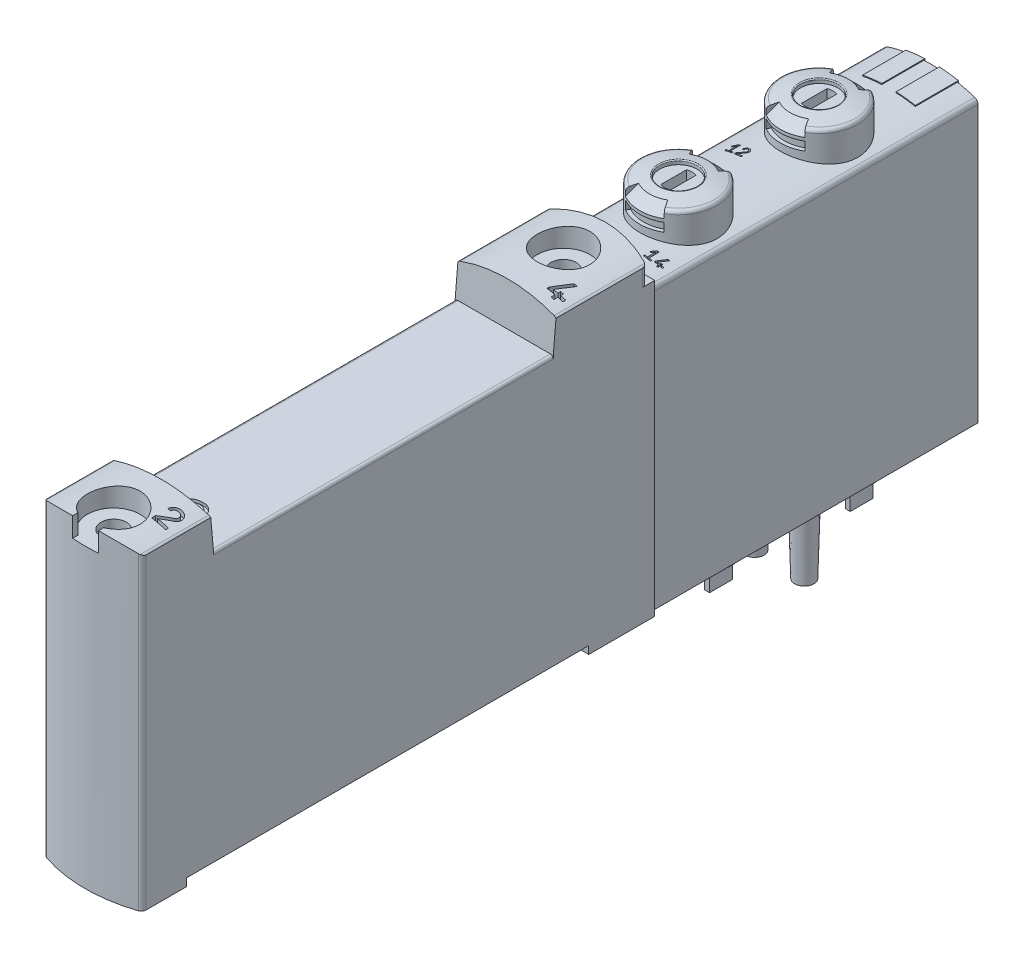
SolidWorks part; units mm, degrees
ref_plane "Ebene vorne" through (0, 0, 0) normal (0, 0, 1) x (1, 0, 0)
ref_plane "Ebene oben" through (0, 0, 0) normal (0, 1, 0) x (1, 0, 0)
ref_plane "Ebene rechts" through (0, 0, 0) normal (1, 0, 0) x (0, 0, -1)
ref_plane "Ebene1" through (0, 0, -23.2) normal (0, 0, 1) x (1, 0, 0)
sketch "Skizze1" plane through (0, 0, -23.2) normal (0, 0, 1) x (1, 0, 0)
  line L0 (-4.9, 29.2163) -> (-4.9, 0)
  line L1 (-4.9, 0) -> (4.9, 0)
  line L2 (4.9, 0) -> (4.9, 29.2163)
  arc A0 (4.9, 29.2163) -> (4.5517, 29.6927) centre (4.4, 29.2163) ccw
  arc A1 (4.5517, 29.6927) -> (-4.5517, 29.6927) centre (0, 15.4) ccw
  arc A2 (-4.5517, 29.6927) -> (-4.9, 29.2163) centre (-4.4, 29.2163) ccw
extrude "Aufsatz-Linear austragen1" add sketch "Skizze1" along normal blind 34
sketch "Skizze2" plane through (0, 0, 0) normal (1, 0, 0) x (0, 0, -1)
  line L0 (-10.88, 0.4) -> (-10.88, 0)
  line L1 (-10.88, 0) -> (23.22, 0)
  line L2 (23.22, 0) -> (23.22, 0.4)
  line L3 (23.22, 0.4) -> (-10.88, 0.4)
extrude "Schnitt-Linear austragen1" cut sketch "Skizze2" along normal blind 6 and the other way blind 6
sketch "Skizze3" plane through (0, 0, 0) normal (0, 1, 0) x (1, 0, 0)
  line L0 (-3.15, 2.4653) -> (-3.15, -2.4653)
  line L1 (3.15, -2.4653) -> (3.15, 2.4653)
  arc A0 (-3.15, -2.4653) -> (3.15, -2.4653) centre (0, 0) ccw
  arc A1 (3.15, 2.4653) -> (-3.15, 2.4653) centre (0, 0) ccw
extrude "Schnitt-Linear austragen2" cut sketch "Skizze3" along normal blind 1.9
sketch "Skizze4" plane through (0, 0, 0) normal (0, 1, 0) x (1, 0, 0)
  line L0 (-3.15, 17.1653) -> (-3.15, 12.2347)
  line L1 (3.15, 12.2347) -> (3.15, 17.1653)
  arc A0 (-3.15, 12.2347) -> (3.15, 12.2347) centre (0, 14.7) ccw
  arc A1 (3.15, 17.1653) -> (-3.15, 17.1653) centre (0, 14.7) ccw
extrude "Schnitt-Linear austragen3" cut sketch "Skizze4" along normal blind 1.9
sketch "Skizze5" plane through (0, 0, 0) normal (1, 0, 0) x (0, 0, -1)
  line L0 (0, 2.1) -> (3.05, 2.1)
  line L1 (3.05, 2.1) -> (3.05, 1.1)
  line L2 (3.05, 1.1) -> (2.25, 1.1)
  line L3 (2.25, 1.1) -> (2.25, -1.4)
  line L4 (2.25, -1.4) -> (2.65, -1.4)
  line L5 (2.65, -1.4) -> (2.65, -1.72)
  line L6 (2.65, -1.72) -> (2.4306, -2.1)
  line L7 (2.4306, -2.1) -> (0, -2.1)
  line L8 (0, -2.1) -> (0, 2.1)
  line L9 (0, -2.1) -> (0, 2.1) construction
revolve "Rotation1" add sketch "Skizze5" angle 360 about L9 reverse direction yes
sketch "Skizze6" plane through (0, 0, 0) normal (1, 0, 0) x (0, 0, -1)
  line L0 (14.7, 2.1) -> (17.75, 2.1)
  line L1 (17.75, 2.1) -> (17.75, 1.1)
  line L2 (17.75, 1.1) -> (16.95, 1.1)
  line L3 (16.95, 1.1) -> (16.95, -1.4)
  line L4 (16.95, -1.4) -> (17.35, -1.4)
  line L5 (17.35, -1.4) -> (17.35, -1.72)
  line L6 (17.35, -1.72) -> (17.1306, -2.1)
  line L7 (17.1306, -2.1) -> (14.7, -2.1)
  line L8 (14.7, -2.1) -> (14.7, 2.1)
  line L9 (14.7, -2.1) -> (14.7, 2.1) construction
revolve "Rotation2" add sketch "Skizze6" angle 360 about L9 reverse direction yes
ref_plane "Ebene2" through (0, 0, -7.35) normal (0, 0, 1) x (1, 0, 0)
sketch "Skizze7" plane through (0, 0, -7.35) normal (0, 0, 1) x (1, 0, 0)
  line L0 (2.6, 0.4) -> (3.8, 0.4)
  line L1 (3.8, 0.4) -> (3.6, -6.9)
  line L2 (2.6, -7.0623) -> (2.6, 0.4)
  line L3 (2.6, -7.0623) -> (2.6, 0.4) construction
  arc A0 (3.6, -6.9) -> (2.6, -7.0623) centre (2.6, -3.9) cw
revolve "Rotation3" add sketch "Skizze7" angle 360 about L3 reverse direction yes
sketch "Skizze8" plane through (0, 0, -7.35) normal (0, 0, 1) x (1, 0, 0)
  line L0 (-2.6, 0.4) -> (-1.4, 0.4)
  line L1 (-1.4, 0.4) -> (-1.6, -6.9)
  line L2 (-2.6, -7.0623) -> (-2.6, 0.4)
  line L3 (-2.6, -7.0623) -> (-2.6, 0.4) construction
  arc A0 (-1.6, -6.9) -> (-2.6, -7.0623) centre (-2.6, -3.9) cw
revolve "Rotation4" add sketch "Skizze8" angle 360 about L3 reverse direction yes
ref_plane "Ebene3" through (0, 0, 0) normal (0, 1, 0) x (1, 0, 0)
ref_plane "Ebene4" through (0, -2.1, 0) normal (0, -1, 0) x (-1, 0, 0)
sketch "Skizze9" plane through (0, -2.1, 0) normal (0, -1, 0) x (-1, 0, 0)
  line L0 (-1.25, -1.2) -> (-0.75, -1.2)
  line L1 (-0.75, -1.2) -> (-0.75, 1.2)
  line L2 (-0.75, 1.2) -> (-1.25, 1.2)
  line L3 (-1.25, 1.2) -> (-1.25, -1.2)
extrude "Aufsatz-Linear austragen2" add sketch "Skizze9" along normal blind 2.5
ref_plane "Ebene5" through (0, -2.1, 0) normal (0, -1, 0) x (-1, 0, 0)
sketch "Skizze10" plane through (0, -2.1, 0) normal (0, -1, 0) x (-1, 0, 0)
  line L0 (0.75, -1.2) -> (1.25, -1.2)
  line L1 (1.25, -1.2) -> (1.25, 1.2)
  line L2 (1.25, 1.2) -> (0.75, 1.2)
  line L3 (0.75, 1.2) -> (0.75, -1.2)
extrude "Aufsatz-Linear austragen3" add sketch "Skizze10" along normal blind 2.5
ref_plane "Ebene6" through (0, -2.1, 0) normal (0, -1, 0) x (-1, 0, 0)
sketch "Skizze11" plane through (0, -2.1, 0) normal (0, -1, 0) x (-1, 0, 0)
  line L0 (-1.25, 13.5) -> (-0.75, 13.5)
  line L1 (-0.75, 13.5) -> (-0.75, 15.9)
  line L2 (-0.75, 15.9) -> (-1.25, 15.9)
  line L3 (-1.25, 15.9) -> (-1.25, 13.5)
extrude "Aufsatz-Linear austragen4" add sketch "Skizze11" along normal blind 2.5
ref_plane "Ebene7" through (0, -2.1, 0) normal (0, -1, 0) x (-1, 0, 0)
sketch "Skizze12" plane through (0, -2.1, 0) normal (0, -1, 0) x (-1, 0, 0)
  line L0 (0.75, 13.5) -> (1.25, 13.5)
  line L1 (1.25, 13.5) -> (1.25, 15.9)
  line L2 (1.25, 15.9) -> (0.75, 15.9)
  line L3 (0.75, 15.9) -> (0.75, 13.5)
extrude "Aufsatz-Linear austragen5" add sketch "Skizze12" along normal blind 2.5
sketch "Skizze13" plane through (0, 0, 0) normal (1, 0, 0) x (0, 0, -1)
  line L0 (-3.2, 33.13) -> (-1.25, 33.13)
  line L1 (-1.25, 33.13) -> (-1.25, 33.4583)
  line L2 (0.85, 32.8364) -> (0.85, 28.4)
  line L3 (0.85, 28.4) -> (-3.2, 28.4)
  line L4 (-3.2, 28.4) -> (-3.2, 33.13)
  line L5 (-3.2, 28.4) -> (-3.2, 33.7) construction
  arc A0 (-1.25, 33.4583) -> (-1.1362, 33.5574) centre (-1.15, 33.4583) cw
  arc A1 (-1.1362, 33.5574) -> (0.55, 33.2237) centre (-3.2, 18.7) cw
  arc A2 (0.55, 33.2237) -> (0.85, 32.8364) centre (0.45, 32.8364) cw
revolve "Rotation5" add sketch "Skizze13" angle 360 about L5 reverse direction yes
sketch "Skizze14" plane through (0, 0, 0) normal (1, 0, 0) x (0, 0, -1)
  line L0 (11.5, 33.13) -> (13.45, 33.13)
  line L1 (13.45, 33.13) -> (13.45, 33.4583)
  line L2 (15.55, 32.8364) -> (15.55, 28.4)
  line L3 (15.55, 28.4) -> (11.5, 28.4)
  line L4 (11.5, 28.4) -> (11.5, 33.13)
  line L5 (11.5, 28.4) -> (11.5, 33.7) construction
  arc A0 (13.45, 33.4583) -> (13.5638, 33.5574) centre (13.55, 33.4583) cw
  arc A1 (13.5638, 33.5574) -> (15.25, 33.2237) centre (11.5, 18.7) cw
  arc A2 (15.25, 33.2237) -> (15.55, 32.8364) centre (15.15, 32.8364) cw
revolve "Rotation6" add sketch "Skizze14" angle 360 about L5 reverse direction yes
sketch "Skizze15" plane through (0, 0, 0) normal (1, 0, 0) x (0, 0, -1)
  line L0 (-0.47, 33.7) -> (0.9, 32.33)
  line L1 (0.9, 32.33) -> (0.9, 32.05)
  line L2 (0.9, 32.05) -> (0.45, 32.05)
  line L3 (0.45, 32.05) -> (0.45, 31.15)
  line L4 (0.45, 31.15) -> (0.9, 31.15)
  line L5 (0.9, 31.15) -> (0.9, 30.5)
  line L6 (0.9, 30.5) -> (1.3, 30.5)
  line L7 (1.3, 30.5) -> (1.3, 33.7)
  line L8 (1.3, 33.7) -> (-0.47, 33.7)
  line L9 (-3.2, 30.5) -> (-3.2, 33.7) construction
revolve "Schnitt-Rotation1" cut sketch "Skizze15" angle 30 about L9 other way angle 30 reverse direction yes
sketch "Skizze16" plane through (0, 0, 0) normal (1, 0, 0) x (0, 0, -1)
  line L0 (-7.7, 30.5) -> (-7.3, 30.5)
  line L1 (-7.3, 30.5) -> (-7.3, 31.15)
  line L2 (-7.3, 31.15) -> (-6.85, 31.15)
  line L3 (-6.85, 31.15) -> (-6.85, 32.05)
  line L4 (-6.85, 32.05) -> (-7.3, 32.05)
  line L5 (-7.3, 32.05) -> (-7.3, 32.33)
  line L6 (-7.3, 32.33) -> (-5.93, 33.7)
  line L7 (-5.93, 33.7) -> (-7.7, 33.7)
  line L8 (-7.7, 33.7) -> (-7.7, 30.5)
  line L9 (-3.2, 33.7) -> (-3.2, 30.5) construction
revolve "Schnitt-Rotation2" cut sketch "Skizze16" angle 30 about L9 other way angle 30 reverse direction yes
ref_plane "Ebene8" through (0, 33.13, 0) normal (0, 1, 0) x (1, 0, 0)
sketch "Skizze17" plane through (0, 33.13, 0) normal (0, 1, 0) x (1, 0, 0)
  line L0 (0.5, -4.5344) -> (0.5, -1.8656)
  line L1 (-0.5, -1.8656) -> (-0.5, -4.5344)
  arc A0 (-0.5, -4.5344) -> (0.5, -4.5344) centre (0, -3.2) ccw
  arc A1 (0.5, -1.8656) -> (-0.5, -1.8656) centre (0, -3.2) ccw
extrude "Schnitt-Linear austragen4" cut sketch "Skizze17" against normal blind 1.7
sketch "Skizze18" plane through (0, 0, 0) normal (1, 0, 0) x (0, 0, -1)
  line L0 (14.23, 33.7) -> (15.6, 32.33)
  line L1 (15.6, 32.33) -> (15.6, 32.05)
  line L2 (15.6, 32.05) -> (15.15, 32.05)
  line L3 (15.15, 32.05) -> (15.15, 31.15)
  line L4 (15.15, 31.15) -> (15.6, 31.15)
  line L5 (15.6, 31.15) -> (15.6, 30.5)
  line L6 (15.6, 30.5) -> (16, 30.5)
  line L7 (16, 30.5) -> (16, 33.7)
  line L8 (16, 33.7) -> (14.23, 33.7)
  line L9 (11.5, 30.5) -> (11.5, 33.7) construction
revolve "Schnitt-Rotation3" cut sketch "Skizze18" angle 30 about L9 other way angle 30 reverse direction yes
sketch "Skizze19" plane through (0, 0, 0) normal (1, 0, 0) x (0, 0, -1)
  line L0 (7, 30.5) -> (7.4, 30.5)
  line L1 (7.4, 30.5) -> (7.4, 31.15)
  line L2 (7.4, 31.15) -> (7.85, 31.15)
  line L3 (7.85, 31.15) -> (7.85, 32.05)
  line L4 (7.85, 32.05) -> (7.4, 32.05)
  line L5 (7.4, 32.05) -> (7.4, 32.33)
  line L6 (7.4, 32.33) -> (8.77, 33.7)
  line L7 (8.77, 33.7) -> (7, 33.7)
  line L8 (7, 33.7) -> (7, 30.5)
  line L9 (11.5, 33.7) -> (11.5, 30.5) construction
revolve "Schnitt-Rotation4" cut sketch "Skizze19" angle 30 about L9 other way angle 30 reverse direction yes
ref_plane "Ebene9" through (0, 33.13, 0) normal (0, 1, 0) x (1, 0, 0)
sketch "Skizze20" plane through (0, 33.13, 0) normal (0, 1, 0) x (1, 0, 0)
  line L0 (0.5, 10.1656) -> (0.5, 12.8344)
  line L1 (-0.5, 12.8344) -> (-0.5, 10.1656)
  arc A0 (-0.5, 10.1656) -> (0.5, 10.1656) centre (0, 11.5) ccw
  arc A1 (0.5, 12.8344) -> (-0.5, 12.8344) centre (0, 11.5) ccw
extrude "Schnitt-Linear austragen5" cut sketch "Skizze20" against normal blind 1.7
ref_plane "Ebene10" through (0, 0, -23.3) normal (0, 0, 1) x (1, 0, 0)
sketch "Skizze21" plane through (0, 0, -23.3) normal (0, 0, 1) x (1, 0, 0)
  line L0 (0.75, 30.4814) -> (0.75, 27)
  line L1 (0.75, 27) -> (2.75, 27)
  line L2 (2.75, 27) -> (2.75, 30.2475)
  arc A0 (2.75, 30.2475) -> (0.75, 30.4814) centre (0, 15.4) ccw
extrude "Aufsatz-Linear austragen6" add sketch "Skizze21" along normal blind 4.5
sketch "Skizze22" plane through (0, 0, -23.3) normal (0, 0, 1) x (1, 0, 0)
  line L0 (-2.75, 30.2475) -> (-2.75, 27)
  line L1 (-2.75, 27) -> (-0.75, 27)
  line L2 (-0.75, 27) -> (-0.75, 30.4814)
  arc A0 (-0.75, 30.4814) -> (-2.75, 30.2475) centre (0, 15.4) ccw
extrude "Aufsatz-Linear austragen7" add sketch "Skizze22" along normal blind 4.5
sketch "Skizze23" plane through (0, 0, 0) normal (0, 1, 0) x (1, 0, 0)
  line L0 (5.125, -63.9426) -> (5.125, -10.8)
  line L1 (5.125, -10.8) -> (-5.125, -10.8)
  line L2 (-5.125, -10.8) -> (-5.125, -63.9426)
  arc A0 (-5.125, -63.9426) -> (-4.7845, -64.4165) centre (-4.625, -63.9426) ccw
  arc A1 (-4.7845, -64.4165) -> (4.7845, -64.4165) centre (0, -50.2) ccw
  arc A2 (4.7845, -64.4165) -> (5.125, -63.9426) centre (4.625, -63.9426) ccw
extrude "Aufsatz-Linear austragen8" add sketch "Skizze23" along normal blind 33.1
sketch "Skizze24" plane through (0, 0, 0) normal (1, 0, 0) x (0, 0, -1)
  line L0 (-57.7749, 38.9) -> (-56.9, 28.9)
  line L1 (-56.9, 28.9) -> (-21.4, 28.9)
  line L2 (-21.4, 28.9) -> (-20.5251, 38.9)
  line L3 (-20.5251, 38.9) -> (-57.7749, 38.9)
extrude "Schnitt-Linear austragen6" cut sketch "Skizze24" along normal blind 10 and the other way blind 10
ref_plane "Ebene11" through (0, 30.4, 0) normal (0, 1, 0) x (1, 0, 0)
sketch "Skizze25" plane through (0, 30.4, 0) normal (0, 1, 0) x (1, 0, 0)
  line L0 (-5.125, -8.8) -> (-5.125, -12.0574)
  line L1 (5.125, -12.0574) -> (5.125, -8.8)
  line L2 (5.125, -8.8) -> (-5.125, -8.8)
  arc A0 (-5.125, -12.0574) -> (-4.7845, -11.5835) centre (-4.625, -12.0574) cw
  arc A1 (-4.7845, -11.5835) -> (4.7845, -11.5835) centre (0, -25.8) cw
  arc A2 (4.7845, -11.5835) -> (5.125, -12.0574) centre (4.625, -12.0574) cw
extrude "Schnitt-Linear austragen7" cut sketch "Skizze25" along normal blind 10
sketch "Skizze26" plane through (0, 0, 0) normal (1, 0, 0) x (0, 0, -1)
  line L0 (-59.7, -0.2) -> (-17.7, -0.2)
  line L1 (-17.7, -0.2) -> (-17.7, 0.8)
  line L2 (-17.7, 0.8) -> (-59.7, 0.8)
  line L3 (-59.7, 0.8) -> (-59.7, -0.2)
extrude "Schnitt-Linear austragen8" cut sketch "Skizze26" along normal blind 10 and the other way blind 10
ref_plane "Ebene12" through (0, 0, 10.8) normal (0, 0, 1) x (1, 0, 0)
sketch "Skizze27" plane through (0, 0, 10.8) normal (0, 0, 1) x (1, 0, 0)
  line L0 (-5.25, 35.1) -> (-5.25, 31.7999)
  line L1 (5.25, 31.7999) -> (5.25, 35.1)
  line L2 (5.25, 35.1) -> (-5.25, 35.1)
  arc A0 (-5.25, 31.7999) -> (-4.9138, 32.2723) centre (-4.75, 31.7999) cw
  arc A1 (-4.9138, 32.2723) -> (4.9138, 32.2723) centre (0, 18.1) cw
  arc A2 (4.9138, 32.2723) -> (5.25, 31.7999) centre (4.75, 31.7999) cw
extrude "Schnitt-Linear austragen9" cut sketch "Skizze27" along normal blind 55
ref_plane "Ebene13" through (0, 0, 21.4) normal (0, 0, 1) x (1, 0, 0)
sketch "Skizze28" plane through (0, 0, 21.4) normal (0, 0, 1) x (1, 0, 0)
  line L0 (-4.825, 28.9) -> (4.825, 28.9)
  line L1 (5.125, 28.6) -> (5.125, 33.6)
  line L2 (5.125, 33.6) -> (-5.125, 33.6)
  line L3 (-5.125, 33.6) -> (-5.125, 28.6)
  arc A0 (-5.125, 28.6) -> (-4.825, 28.9) centre (-4.825, 28.6) cw
  arc A1 (4.825, 28.9) -> (5.125, 28.6) centre (4.825, 28.6) cw
extrude "Schnitt-Linear austragen10" cut sketch "Skizze28" along normal blind 35.5
ref_plane "Ebene14" through (0, 33.1, 0) normal (0, 1, 0) x (1, 0, 0)
sketch "Skizze29" plane through (0, 33.1, 0) normal (0, 1, 0) x (1, 0, 0)
  line L0 (-1.35, -64.5958) -> (-1.35, -66)
  line L1 (-1.35, -66) -> (1.35, -66)
  line L2 (1.35, -66) -> (1.35, -64.5958)
  arc A0 (1.35, -64.5958) -> (-1.35, -64.5958) centre (0, -62.2) ccw
extrude "Schnitt-Linear austragen11" cut sketch "Skizze29" along normal blind 2.1 and the other way blind 2.1
sketch "Skizze30" plane through (0, 0, 0) normal (1, 0, 0) x (0, 0, -1)
  line L0 (-62.2, 31) -> (-60.875, 31)
  line L1 (-60.875, 31) -> (-60.875, 0)
  line L2 (-60.875, 0) -> (-62.2, 0)
  line L3 (-62.2, 0) -> (-62.2, 31)
  line L4 (-62.2, 0) -> (-62.2, 31) construction
revolve "Schnitt-Rotation5" cut sketch "Skizze30" angle 360 about L4 reverse direction yes
sketch "Skizze31" plane through (0, 0, 0) normal (1, 0, 0) x (0, 0, -1)
  line L0 (-15.2, 33.2) -> (-12.45, 33.2)
  line L1 (-12.45, 33.2) -> (-12.45, 31)
  line L2 (-12.45, 31) -> (-13.875, 31)
  line L3 (-13.875, 31) -> (-13.875, 0)
  line L4 (-13.875, 0) -> (-15.2, 0)
  line L5 (-15.2, 0) -> (-15.2, 33.2)
  line L6 (-15.2, 0) -> (-15.2, 33.2) construction
revolve "Schnitt-Rotation6" cut sketch "Skizze31" angle 360 about L6 reverse direction yes
ref_plane "Ebene15" through (1.605, 0, 0) normal (1, 0, 0) x (0, 0, -1)
sketch "Skizze32" plane through (0, 0, 0) normal (1, 0, 0) x (0, 0, -1)
  line L0 (-40.2, 9.8) -> (-38.1, 9.8)
  line L1 (-38.1, 9.8) -> (-38.1, 1.8)
  line L2 (-38.1, 1.8) -> (-37.4, 1.8)
  line L3 (-37.4, 1.8) -> (-37.4, 0.8)
  line L4 (-37.4, 0.8) -> (-40.2, 0.8)
  line L5 (-40.2, 0.8) -> (-40.2, 9.8)
  line L6 (-40.2, 0.8) -> (-40.2, 9.8) construction
revolve "Schnitt-Rotation7" cut sketch "Skizze32" angle 360 about L6 reverse direction yes
ref_plane "Ebene16" through (-1.55, 0, 0) normal (1, 0, 0) x (0, 0, -1)
sketch "Skizze33" plane through (-1.55, 0, 0) normal (1, 0, 0) x (0, 0, -1)
  line L0 (-29.1, 9.8) -> (-27, 9.8)
  line L1 (-27, 9.8) -> (-27, 1.8)
  line L2 (-27, 1.8) -> (-26.3, 1.8)
  line L3 (-26.3, 1.8) -> (-26.3, 0.8)
  line L4 (-26.3, 0.8) -> (-29.1, 0.8)
  line L5 (-29.1, 0.8) -> (-29.1, 9.8)
  line L6 (-29.1, 0.8) -> (-29.1, 9.8) construction
revolve "Schnitt-Rotation8" cut sketch "Skizze33" angle 360 about L6 reverse direction yes
sketch "Skizze34" plane through (-1.55, 0, 0) normal (1, 0, 0) x (0, 0, -1)
  line L0 (-46.1, 9.8) -> (-44, 9.8)
  line L1 (-44, 9.8) -> (-44, 1.8)
  line L2 (-44, 1.8) -> (-43.3, 1.8)
  line L3 (-43.3, 1.8) -> (-43.3, 0.8)
  line L4 (-43.3, 0.8) -> (-46.1, 0.8)
  line L5 (-46.1, 0.8) -> (-46.1, 9.8)
  line L6 (-46.1, 0.8) -> (-46.1, 9.8) construction
revolve "Schnitt-Rotation9" cut sketch "Skizze34" angle 360 about L6 reverse direction yes
ref_plane "Ebene17" through (1.55, 0, 0) normal (1, 0, 0) x (0, 0, -1)
sketch "Skizze35" plane through (1.55, 0, 0) normal (1, 0, 0) x (0, 0, -1)
  line L0 (-34.3, 9.8) -> (-32.2, 9.8)
  line L1 (-32.2, 9.8) -> (-32.2, 1.8)
  line L2 (-32.2, 1.8) -> (-31.5, 1.8)
  line L3 (-31.5, 1.8) -> (-31.5, 0.8)
  line L4 (-31.5, 0.8) -> (-34.3, 0.8)
  line L5 (-34.3, 0.8) -> (-34.3, 9.8)
  line L6 (-34.3, 0.8) -> (-34.3, 9.8) construction
revolve "Schnitt-Rotation10" cut sketch "Skizze35" angle 360 about L6 reverse direction yes
sketch "Skizze36" plane through (1.55, 0, 0) normal (1, 0, 0) x (0, 0, -1)
  line L0 (-51.3, 9.8) -> (-49.2, 9.8)
  line L1 (-49.2, 9.8) -> (-49.2, 1.8)
  line L2 (-49.2, 1.8) -> (-48.5, 1.8)
  line L3 (-48.5, 1.8) -> (-48.5, 0.8)
  line L4 (-48.5, 0.8) -> (-51.3, 0.8)
  line L5 (-51.3, 0.8) -> (-51.3, 9.8)
  line L6 (-51.3, 0.8) -> (-51.3, 9.8) construction
revolve "Schnitt-Rotation11" cut sketch "Skizze36" angle 360 about L6 reverse direction yes
ref_plane "Ebene18" through (0, 33.53, 0) normal (0, 1, 0) x (1, 0, 0)
ref_plane "Ebene19" through (0, 28.9, 0) normal (0, 1, 0) x (1, 0, 0)
ref_plane "Ebene20" through (0, 0.8, 0) normal (0, 1, 0) x (1, 0, 0)
ref_plane "Ebene21" through (0, 33.1, 0) normal (0, 1, 0) x (1, 0, 0)
sketch "Skizze37" plane through (0, 33.1, 0) normal (0, 1, 0) x (1, 0, 0)
  line L0 (-3.3985, 5.738) -> (-3.2978, 5.6676)
  line L1 (-3.2978, 5.6676) -> (-3.075, 5.9858)
  line L2 (-3.075, 5.9858) -> (-3.075, 5.15)
  line L3 (-3.075, 5.15) -> (-3.375, 5.15)
  line L4 (-3.375, 5.15) -> (-3.375, 5)
  line L5 (-3.375, 5) -> (-2.625, 5)
  line L6 (-2.625, 5) -> (-2.625, 5.15)
  line L7 (-2.625, 5.15) -> (-2.925, 5.15)
  line L8 (-2.925, 5.15) -> (-2.925, 6.2)
  line L9 (-2.925, 6.2) -> (-3.075, 6.2)
  line L10 (-3.075, 6.2) -> (-3.3985, 5.738)
extrude "Schnitt-Linear austragen12" cut sketch "Skizze37" along normal blind 3.5 and the other way blind 3.5
sketch "Skizze38" plane through (0, 33.1, 0) normal (0, 1, 0) x (1, 0, 0)
  line L0 (-2.3625, 5.8375) -> (-2.2125, 5.8375)
  line L1 (-1.8546, 5.6826) -> (-2.3625, 5.2057)
  line L2 (-2.3625, 5.2057) -> (-2.3625, 5)
  line L3 (-2.3625, 5) -> (-1.6375, 5)
  line L4 (-1.6375, 5) -> (-1.6375, 5.15)
  line L5 (-1.6375, 5.15) -> (-2.2027, 5.15)
  line L6 (-2.2027, 5.15) -> (-1.7519, 5.5732)
  arc A0 (-2.2125, 5.8375) -> (-1.8546, 5.6826) centre (-2, 5.8375) cw
  arc A1 (-1.7519, 5.5732) -> (-2.3625, 5.8375) centre (-2, 5.8375) ccw
extrude "Schnitt-Linear austragen13" cut sketch "Skizze38" along normal blind 3.5 and the other way blind 3.5
sketch "Skizze39" plane through (0, 33.1, 0) normal (0, 1, 0) x (1, 0, 0)
  line L0 (2.1015, -8.262) -> (2.2022, -8.3324)
  line L1 (2.2022, -8.3324) -> (2.425, -8.0142)
  line L2 (2.425, -8.0142) -> (2.425, -8.85)
  line L3 (2.425, -8.85) -> (2.125, -8.85)
  line L4 (2.125, -8.85) -> (2.125, -9)
  line L5 (2.125, -9) -> (2.875, -9)
  line L6 (2.875, -9) -> (2.875, -8.85)
  line L7 (2.875, -8.85) -> (2.575, -8.85)
  line L8 (2.575, -8.85) -> (2.575, -7.8)
  line L9 (2.575, -7.8) -> (2.425, -7.8)
  line L10 (2.425, -7.8) -> (2.1015, -8.262)
extrude "Schnitt-Linear austragen14" cut sketch "Skizze39" along normal blind 3.5 and the other way blind 3.5
sketch "Skizze40" plane through (0, 33.1, 0) normal (0, 1, 0) x (1, 0, 0)
  line L0 (3.085, -8.8) -> (3.5, -8.8)
  line L1 (3.5, -8.8) -> (3.5, -9)
  line L2 (3.5, -9) -> (3.65, -9)
  line L3 (3.65, -9) -> (3.65, -8.8)
  line L4 (3.65, -8.8) -> (3.915, -8.8)
  line L5 (3.915, -8.8) -> (3.915, -8.65)
  line L6 (3.915, -8.65) -> (3.65, -8.65)
  line L7 (3.65, -8.65) -> (3.65, -8.5)
  line L8 (3.65, -8.5) -> (3.5, -8.5)
  line L9 (3.5, -8.5) -> (3.5, -8.65)
  line L10 (3.5, -8.65) -> (3.2699, -8.65)
  line L11 (3.2699, -8.65) -> (3.6663, -7.8)
  line L12 (3.6663, -7.8) -> (3.5008, -7.8)
  line L13 (3.5008, -7.8) -> (3.085, -8.6917)
  line L14 (3.085, -8.6917) -> (3.085, -8.8)
extrude "Schnitt-Linear austragen15" cut sketch "Skizze40" along normal blind 3.5 and the other way blind 3.5
sketch "Skizze41" plane through (0, 33.1, 0) normal (0, 1, 0) x (1, 0, 0)
  line L0 (2.67, -19.6) -> (3.5, -19.6)
  line L1 (3.5, -19.6) -> (3.5, -20)
  line L2 (3.5, -20) -> (3.8, -20)
  line L3 (3.8, -20) -> (3.8, -19.6)
  line L4 (3.8, -19.6) -> (4.33, -19.6)
  line L5 (4.33, -19.6) -> (4.33, -19.3)
  line L6 (4.33, -19.3) -> (3.8, -19.3)
  line L7 (3.8, -19.3) -> (3.8, -19)
  line L8 (3.8, -19) -> (3.5, -19)
  line L9 (3.5, -19) -> (3.5, -19.3)
  line L10 (3.5, -19.3) -> (3.0399, -19.3)
  line L11 (3.0399, -19.3) -> (3.8326, -17.6)
  line L12 (3.8326, -17.6) -> (3.5016, -17.6)
  line L13 (3.5016, -17.6) -> (2.67, -19.3834)
  line L14 (2.67, -19.3834) -> (2.67, -19.6)
extrude "Schnitt-Linear austragen16" cut sketch "Skizze41" along normal blind 1 and the other way blind 1
sketch "Skizze42" plane through (0, 33.1, 0) normal (0, 1, 0) x (1, 0, 0)
  line L0 (2.775, -59.325) -> (3.075, -59.325)
  line L1 (3.7909, -59.6349) -> (2.775, -60.5885)
  line L2 (2.775, -60.5885) -> (2.775, -61)
  line L3 (2.775, -61) -> (4.225, -61)
  line L4 (4.225, -61) -> (4.225, -60.7)
  line L5 (4.225, -60.7) -> (3.0946, -60.7)
  line L6 (3.0946, -60.7) -> (3.9962, -59.8536)
  arc A0 (3.075, -59.325) -> (3.7909, -59.6349) centre (3.5, -59.325) cw
  arc A1 (3.9962, -59.8536) -> (2.775, -59.325) centre (3.5, -59.325) ccw
extrude "Schnitt-Linear austragen17" cut sketch "Skizze42" along normal blind 1 and the other way blind 1
sketch "Skizze43" plane through (0, 33.1, 0) normal (0, 1, 0) x (1, 0, 0)
  line L0 (1.02, -55.5539) -> (1.02, -56)
  line L1 (1.02, -56) -> (1.38, -56)
  line L2 (1.38, -56) -> (1.38, -54.35)
  line L3 (1.38, -54.35) -> (0.06, -54.35)
  line L4 (0.06, -54.35) -> (0.06, -54.71)
  line L5 (0.06, -54.71) -> (1.02, -54.71)
  line L6 (-1.02, -54.71) -> (-1.02, -54.38)
  line L7 (1.02, -53.9) -> (1.38, -53.9)
  line L8 (0.4267, -53) -> (0, -53)
  line L9 (-1.38, -54.38) -> (-1.38, -54.71)
  arc A0 (-1.38, -54.71) -> (1.02, -55.5539) centre (0, -54.62) ccw
  arc A1 (1.02, -54.71) -> (-1.02, -54.71) centre (0, -54.62) cw
  arc A2 (-1.02, -54.38) -> (0, -53.36) centre (0.0584, -54.4384) cw
  arc A3 (0, -53.36) -> (1.02, -53.9) centre (0.1869, -54.2404) cw
  arc A4 (1.38, -53.9) -> (0.4267, -53) centre (0.2133, -54.1809) ccw
  arc A5 (0, -53) -> (-1.38, -54.38) centre (0, -54.38) ccw
extrude "Schnitt-Linear austragen18" cut sketch "Skizze43" along normal blind 4.5 and the other way blind 4.5
ref_plane "ANBAU XY" through (0, 0, 0) normal (0, 1, 0) x (1, 0, 0)
ref_plane "ANBAU XZ" through (0, 0, 0) normal (-1, 0, 0) x (0, 0, 1)
ref_plane "ANBAU YZ" through (0, 0, -14.7) normal (0, 0, 1) x (1, 0, 0)
ref_axis "ANBAU X" through (0, 0, -50) along (0, 0, 1)
ref_axis "ANBAU Y" through (-80.9, 0, -14.7) along (1, 0, 0)
ref_axis "ANBAU Z" through (0, 50, -14.7) along (0, -1, 0)
sketch3d "ANBAU"
  point P0 (0, 0, -14.7)
ref_plane "DICHTUNG XY" through (0, 0.8, 0) normal (0, 1, 0) x (1, 0, 0)
ref_plane "DICHTUNG XZ" through (0, 0, 0) normal (-1, 0, 0) x (0, 0, 1)
ref_plane "DICHTUNG YZ" through (0, 0, 40.2) normal (0, 0, 1) x (1, 0, 0)
ref_axis "DICHTUNG X" through (0, 0.8, -50) along (0, 0, 1)
ref_axis "DICHTUNG Y" through (-80.9, 0.8, 40.2) along (1, 0, 0)
ref_axis "DICHTUNG Z" through (0, 50, 40.2) along (0, -1, 0)
sketch3d "DICHTUNG"
  point P0 (0, 0.8, 40.2)
ref_plane "GEHAUSE XY" through (0, 0.8, 0) normal (0, 1, 0) x (1, 0, 0)
ref_plane "GEHAUSE XZ" through (0, 0, 0) normal (-1, 0, 0) x (0, 0, 1)
ref_plane "GEHAUSE YZ" through (0, 0, 38.7) normal (0, 0, 1) x (1, 0, 0)
ref_axis "GEHAUSE X" through (0, 0.8, -50) along (0, 0, 1)
ref_axis "GEHAUSE Y" through (-80.9, 0.8, 38.7) along (1, 0, 0)
ref_axis "GEHAUSE Z" through (0, 50, 38.7) along (0, -1, 0)
sketch3d "GEHAUSE"
  point P0 (0, 0.8, 38.7)
ref_plane "HHB1 XY" through (0, 33.53, 0) normal (0, 1, 0) x (1, 0, 0)
ref_plane "HHB1 XZ" through (0, 0, 0) normal (1, 0, 0) x (0, 0, -1)
ref_plane "HHB1 YZ" through (0, 0, -11.5) normal (0, 0, -1) x (-1, 0, 0)
ref_axis "HHB1 X" through (0, 33.53, 50) along (0, 0, -1)
ref_axis "HHB1 Y" through (80.9, 33.53, -11.5) along (-1, 0, 0)
ref_axis "HHB1 Z" through (0, 50, -11.5) along (0, -1, 0)
sketch3d "HHB1"
  point P0 (0, 33.53, -11.5)
ref_plane "HHB2 XY" through (0, 33.53, 0) normal (0, 1, 0) x (1, 0, 0)
ref_plane "HHB2 XZ" through (0, 0, 0) normal (1, 0, 0) x (0, 0, -1)
ref_plane "HHB2 YZ" through (0, 0, 3.2) normal (0, 0, -1) x (-1, 0, 0)
ref_axis "HHB2 X" through (0, 33.53, 50) along (0, 0, -1)
ref_axis "HHB2 Y" through (80.9, 33.53, 3.2) along (-1, 0, 0)
ref_axis "HHB2 Z" through (0, 50, 3.2) along (0, -1, 0)
sketch3d "HHB2"
  point P0 (0, 33.53, 3.2)
ref_plane "QS1 XY" through (0, 28.9, 0) normal (0, -1, 0) x (-1, 0, 0)
ref_plane "QS1 XZ" through (0, 0, 0) normal (-1, 0, 0) x (0, 0, 1)
ref_plane "QS1 YZ" through (0, 0, 46.2) normal (0, 0, -1) x (-1, 0, 0)
ref_axis "QS1 X" through (0, 28.9, 50) along (0, 0, -1)
ref_axis "QS1 Y" through (-80.9, 28.9, 46.2) along (1, 0, 0)
ref_axis "QS1 Z" through (0, -50, 46.2) along (0, 1, 0)
sketch3d "QS1"
  point P0 (0, 28.9, 46.2)
ref_plane "QS2 XY" through (0, 28.9, 0) normal (0, -1, 0) x (-1, 0, 0)
ref_plane "QS2 XZ" through (0, 0, 0) normal (-1, 0, 0) x (0, 0, 1)
ref_plane "QS2 YZ" through (0, 0, 34.2) normal (0, 0, -1) x (-1, 0, 0)
ref_axis "QS2 X" through (0, 28.9, 50) along (0, 0, -1)
ref_axis "QS2 Y" through (-80.9, 28.9, 34.2) along (1, 0, 0)
ref_axis "QS2 Z" through (0, -50, 34.2) along (0, 1, 0)
sketch3d "QS2"
  point P0 (0, 28.9, 34.2)
ref_plane "SCREW1 XY" through (0, 31, 0) normal (0, 1, 0) x (1, 0, 0)
ref_plane "SCREW1 XZ" through (0, 0, 0) normal (1, 0, 0) x (0, 0, -1)
ref_plane "SCREW1 YZ" through (0, 0, 15.2) normal (0, 0, -1) x (-1, 0, 0)
ref_axis "SCREW1 X" through (0, 31, 50) along (0, 0, -1)
ref_axis "SCREW1 Y" through (80.9, 31, 15.2) along (-1, 0, 0)
ref_axis "SCREW1 Z" through (0, 50, 15.2) along (0, -1, 0)
sketch3d "SCREW1"
  point P0 (0, 31, 15.2)
ref_plane "SCREW2 XY" through (0, 31, 0) normal (0, 1, 0) x (1, 0, 0)
ref_plane "SCREW2 XZ" through (0, 0, 0) normal (1, 0, 0) x (0, 0, -1)
ref_plane "SCREW2 YZ" through (0, 0, 62.2) normal (0, 0, -1) x (-1, 0, 0)
ref_axis "SCREW2 X" through (0, 31, 50) along (0, 0, -1)
ref_axis "SCREW2 Y" through (80.9, 31, 62.2) along (-1, 0, 0)
ref_axis "SCREW2 Z" through (0, 50, 62.2) along (0, -1, 0)
sketch3d "SCREW2"
  point P0 (0, 31, 62.2)
ref_plane "TO_DUMMY XY" through (0, 0, 0) normal (0, -1, 0) x (-1, 0, 0)
ref_plane "TO_DUMMY XZ" through (0, 0, 0) normal (1, 0, 0) x (0, 0, -1)
ref_plane "TO_DUMMY YZ" through (0, 0, 38.7) normal (0, 0, 1) x (1, 0, 0)
ref_axis "TO_DUMMY X" through (0, 0, -50) along (0, 0, 1)
ref_axis "TO_DUMMY Y" through (80.9, 0, 38.7) along (-1, 0, 0)
ref_axis "TO_DUMMY Z" through (0, -50, 38.7) along (0, 1, 0)
sketch3d "TO_DUMMY"
  point P0 (0, 0, 38.7)
ref_plane "U1 XY" through (0, 0.8, 0) normal (0, 1, 0) x (1, 0, 0)
ref_plane "U1 XZ" through (0, 0, 0) normal (1, 0, 0) x (0, 0, -1)
ref_plane "U1 YZ" through (0, 0, 29.2) normal (0, 0, -1) x (-1, 0, 0)
ref_axis "U1 X" through (0, 0.8, 50) along (0, 0, -1)
ref_axis "U1 Y" through (80.9, 0.8, 29.2) along (-1, 0, 0)
ref_axis "U1 Z" through (0, 50, 29.2) along (0, -1, 0)
sketch3d "U1"
  point P0 (0, 0.8, 29.2)
ref_plane "U2 XY" through (0, 0.8, 0) normal (0, 1, 0) x (1, 0, 0)
ref_plane "U2 XZ" through (0, 0, 0) normal (1, 0, 0) x (0, 0, -1)
ref_plane "U2 YZ" through (0, 0, 51.2) normal (0, 0, -1) x (-1, 0, 0)
ref_axis "U2 X" through (0, 0.8, 50) along (0, 0, -1)
ref_axis "U2 Y" through (80.9, 0.8, 51.2) along (-1, 0, 0)
ref_axis "U2 Z" through (0, 50, 51.2) along (0, -1, 0)
sketch3d "U2"
  point P0 (0, 0.8, 51.2)
